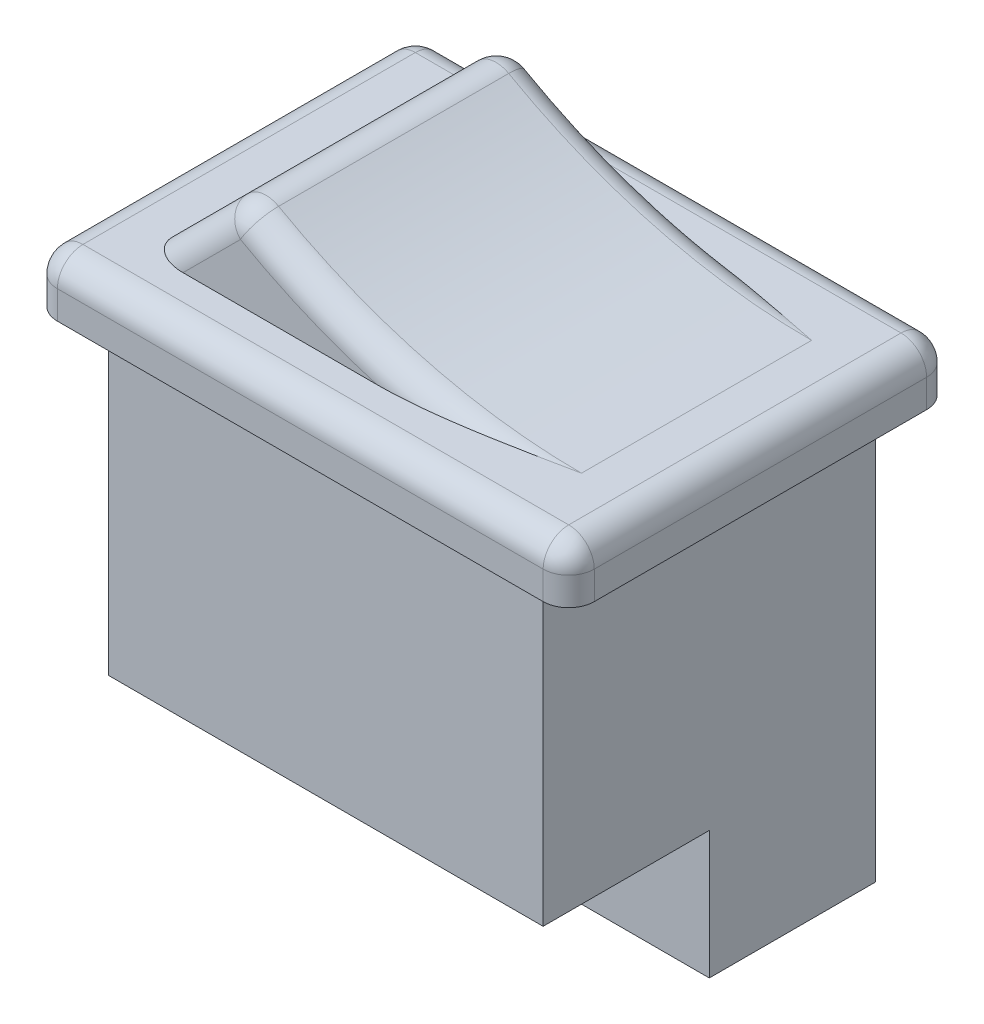
SolidWorks part; units mm, degrees
material "7075-T6 (SN)"
ref_plane "正面" through (0, 0, 0) normal (0, 0, 1) x (1, 0, 0)
ref_plane "平面" through (0, 0, 0) normal (0, 1, 0) x (1, 0, 0)
ref_plane "右側面" through (0, 0, 0) normal (1, 0, 0) x (0, 0, -1)
sketch "ｽｹｯﾁ1" plane through (0, 0, 0) normal (0, 1, 0) x (1, 0, 0)
  line L1 (-10.5, 7.5) -> (10.5, 7.5)
  line L2 (-10.5, 7.5) -> (-10.5, -7.5)
  line L3 (-10.5, -7.5) -> (10.5, -7.5)
  line L4 (10.5, 7.5) -> (10.5, -7.5)
  line L5 (-10.5, 7.5) -> (10.5, -7.5) construction
  line L6 (-10.5, -7.5) -> (10.5, 7.5) construction
  point P0 (0, 0)
  dimension "D1" = 21
  dimension "D2" = 15
extrude "ﾎﾞｽ - 押し出し1" add sketch "ｽｹｯﾁ1" along normal blind 2.1
sketch "ｽｹｯﾁ2" plane through (0, 0, 0) normal (0, 0, 1) x (1, 0, 0)
  line L0 (10.5, 2.1) -> (10.5, 0) construction
  line L1 (-10.5, 2.1) -> (10.5, 2.1) construction
  line L2 (-8, 2.1) -> (-4.5, 5.6)
  line L3 (-8, 2.1) -> (8, 2.1)
  line L4 (-10.5, 2.1) -> (-10.5, 0) construction
  arc A0 (-4.5, 5.6) -> (8, 2.1) centre (8, 26.1714) ccw
  dimension "D1" = 2.5
  dimension "D2" = 2.5
  dimension "D3" = 3.5
  dimension "D4" = 3.5
extrude "ﾎﾞｽ - 押し出し2" add sketch "ｽｹｯﾁ2" along normal mid plane 11
fillet "ﾌｨﾚｯﾄ1" radius 1 5 edges at (-6.25, 3.85, -5.5) (1.5096, 2.9915, -5.5) (1.5096, 2.9915, 5.5) (-6.25, 3.85, 5.5) (-4.5, 5.6, 0)
sketch "ｽｹｯﾁ3" plane through (0, 0, 0) normal (0, -1, 0) x (1, 0, 0)
  line L1 (-8.5, 6.5) -> (8.5, 6.5)
  line L2 (-8.5, 6.5) -> (-8.5, -6.5)
  line L3 (-8.5, -6.5) -> (8.5, -6.5)
  line L4 (8.5, 6.5) -> (8.5, -6.5)
  line L5 (-8.5, 6.5) -> (8.5, -6.5) construction
  line L6 (-8.5, -6.5) -> (8.5, 6.5) construction
  point P0 (0, 0)
  dimension "D1" = 17
  dimension "D2" = 13
extrude "ﾎﾞｽ - 押し出し3" add sketch "ｽｹｯﾁ3" along normal blind 12
fillet "ﾌｨﾚｯﾄ2" radius 1 8 edges at (-10.5, 1.05, 7.5) (-10.5, 1.05, -7.5) (10.5, 1.05, -7.5) (10.5, 1.05, 7.5) (-10.5, 2.1, 0) (0, 2.1, -7.5) (10.5, 2.1, 0) (0, 2.1, 7.5)
sketch "ｽｹｯﾁ4" plane through (0, -12, 0) normal (0, -1, 0) x (1, 0, 0)
  line L0 (-8.5, -6.5) -> (8.5, -6.5) construction
  line L1 (-8.5, -6.5) -> (8.5, -6.5)
  line L2 (-8.5, -6.5) -> (-8.5, 0)
  line L3 (-8.5, 0) -> (8.5, 0)
  line L4 (8.5, -6.5) -> (8.5, 0)
  line L5 (-8.5, -6.5) -> (8.5, 0) construction
  line L6 (-8.5, 0) -> (8.5, -6.5) construction
  line L7 (8.5, -6.5) -> (8.5, 6.5) construction
  line L8 (-8.5, 6.5) -> (-8.5, -6.5) construction
  point P4 (0, -3.25)
  dimension "D1" = 6.5
extrude "ﾎﾞｽ - 押し出し4" add sketch "ｽｹｯﾁ4" along normal blind 5
